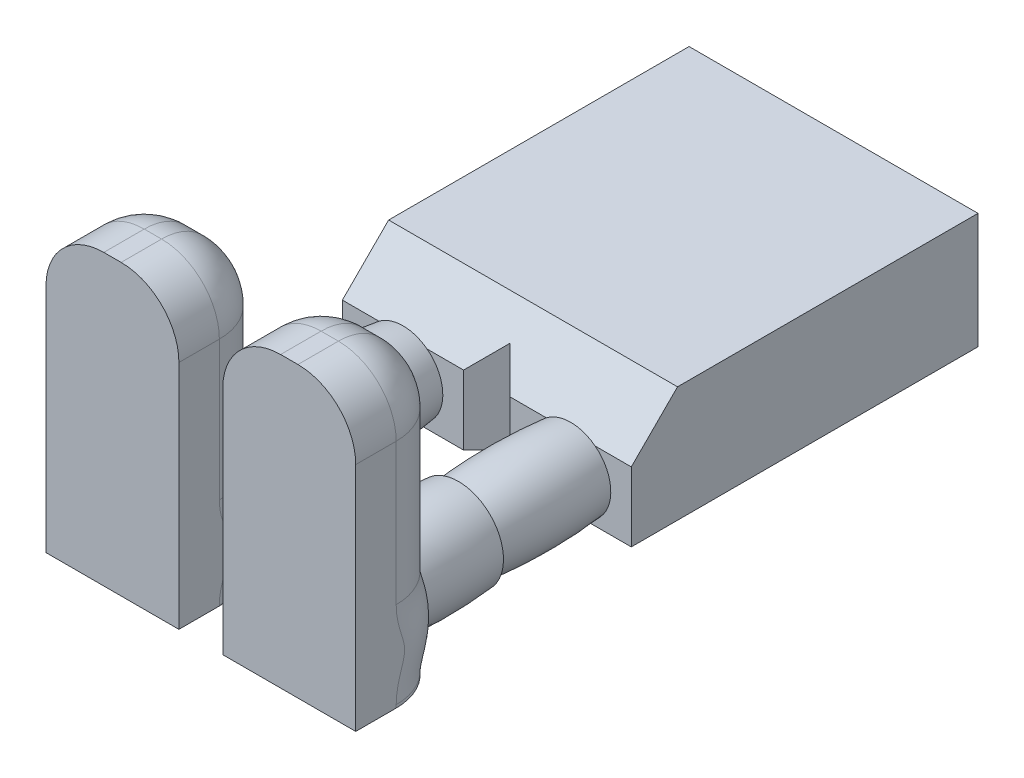
SolidWorks part; units mm, degrees
ref_plane "Alzado" through (0, 0, 0) normal (0, 0, 1) x (1, 0, 0)
ref_plane "Planta" through (0, 0, 0) normal (0, 1, 0) x (1, 0, 0)
ref_plane "Vista lateral" through (0, 0, 0) normal (1, 0, 0) x (0, 0, -1)
sketch "Croquis1" plane through (0, 0, 0) normal (0, 1, 0) x (1, 0, 0)
  line L2 (-26.073, 6.2713) -> (-26.073, -43.7287)
  line L3 (-26.073, -43.7287) -> (23.927, -43.7287)
  line L4 (23.927, 6.2713) -> (23.927, -43.7287)
  line L6 (23.927, 6.2713) -> (23.927, 16.2713)
  line L7 (23.927, 16.2713) -> (-26.073, 16.2713)
  line L8 (-26.073, 6.2713) -> (-26.073, 16.2713)
extrude "Saliente-Extruir1" add sketch "Croquis1" along normal blind 20
sketch "Croquis2" plane through (0, 20, 0) normal (0, 1, 0) x (1, 0, 0)
  line L0 (-1.073, -43.7287) -> (-1.073, -39.7013)
  line L1 (-26.073, -43.7287) -> (23.927, -43.7287) construction
  line L2 (-1.073, -39.7013) -> (-5.1004, -43.7287)
  line L3 (-5.1004, -43.7287) -> (2.0438, -43.7287)
  line L4 (-1.073, -39.7013) -> (2.9544, -43.7287)
  line L5 (2.9544, -43.7287) -> (2.0438, -43.7287)
  line M2 (-26.073, -43.7287) -> (23.927, -43.7287)
extrude "Cortar-Extruir1" cut sketch "Croquis2" against normal blind 20 contours L0 L2 M2 | L4 L0 M2 region at (-2.4155, 20, 42.3863) region at (0.2695, 20, 42.3863)
chamfer "Chaflán1" distance 8 angle 45 1 edges at (13.4407, 20, 43.7287)
ref_plane "Plano1" through (0, 6.5, 0) normal (0, 1, 0) x (1, 0, 0)
sketch "Croquis3" plane through (0, 6.5, 0) normal (0, 1, 0) x (1, 0, 0)
  line L0 (-15.5867, -43.7287) -> (-15.5867, -76.7287)
  line L1 (-5.1004, -43.7287) -> (-26.073, -43.7287) construction
  line L2 (-15.5867, -76.7287) -> (-23.5867, -76.7287)
  line L3 (-15.5867, -43.7287) -> (-18.4824, -43.7287)
  line L4 (-23.3723, -62.9885) -> (-24.3723, -62.9885)
  line L5 (-18.4824, -43.7287) -> (-22.4824, -43.7287)
  line L6 (-5.1004, -43.7287) -> (-26.073, -43.7287) construction
  spline S0 degree 2 poles (-24.3723, -62.9885) (-24.8041, -69.7441) (-23.5867, -76.7287) knots 0.593779 0.593779 0.593779 1 1 1
  spline S2 degree 2 poles (-22.4824, -43.7287) (-23.8858, -53.3109) (-23.3723, -62.9885) knots 0 0 0 1 1 1
revolve "Revolución1" add sketch "Croquis3" angle 360 about L0
sketch "Croquis4" plane through (0, 6.5, 0) normal (0, 1, 0) x (1, 0, 0)
  line L0 (13.4407, -43.7287) -> (13.4407, -76.7287)
  line L1 (23.927, -43.7287) -> (2.9544, -43.7287) construction
  line L2 (13.4407, -76.7287) -> (5.4407, -76.7287)
  line L3 (13.4407, -43.7287) -> (10.5039, -43.7287)
  line L4 (5.6604, -63.1443) -> (6.6604, -63.1443)
  line L5 (10.5039, -43.7287) -> (6.5039, -43.7287)
  spline S0 degree 3 poles (5.6604, -63.1443) (5.263, -67.6438) (5.1898, -72.172) (5.4407, -76.7287) knots 0.592131 0.592131 0.592131 0.592131 1 1 1 1
  spline S3 degree 2 poles (6.5039, -43.7287) (5.5942, -53.4498) (6.6604, -63.1443) knots 0 0 0 1 1 1
revolve "Revolución2" add sketch "Croquis4" angle 360 about L0
sketch "Croquis5" plane through (0, 0, 76.7287) normal (0, 0, 1) x (1, 0, 0)
  line L1 (-27.3649, -1.5) -> (-4.3649, -1.5)
  line L8 (-27.3649, -1.5) -> (-27.3649, 38.5)
  line L9 (-17.3649, 48.5) -> (-14.3649, 48.5)
  line L10 (-4.3649, -1.5) -> (-4.3649, 38.5)
  line L11 (3.2371, -1.5) -> (26.2371, -1.5)
  line L12 (3.2371, -1.5) -> (3.2371, 38.5)
  line L13 (13.2371, 48.5) -> (16.2371, 48.5)
  line L14 (26.2371, -1.5) -> (26.2371, 38.5)
  arc A8 (-14.3649, 48.5) -> (-4.3649, 38.5) centre (-14.3649, 38.5) cw
  arc A9 (-27.3649, 38.5) -> (-17.3649, 48.5) centre (-17.3649, 38.5) cw
  arc A10 (16.2371, 48.5) -> (26.2371, 38.5) centre (16.2371, 38.5) cw
  arc A11 (13.2371, 48.5) -> (3.2371, 38.5) centre (13.2371, 38.5) ccw
  dimension "D2" = 10
  dimension "D3" = 10
extrude "Saliente-Extruir2" add sketch "Croquis5" along normal blind 17
fillet "Redondeo1" radius 10 10 edges at (26.2371, 18.5, 76.7287) (23.3082, 45.5711, 76.7287) (14.7371, 48.5, 76.7287) (6.166, 45.5711, 76.7287) (-4.3649, 18.5, 76.7287) (-7.2939, 45.5711, 76.7287) (-15.8649, 48.5, 76.7287) (-24.436, 45.5711, 76.7287) (3.2371, 18.5, 76.7287) (-27.3649, 18.5, 76.7287)
